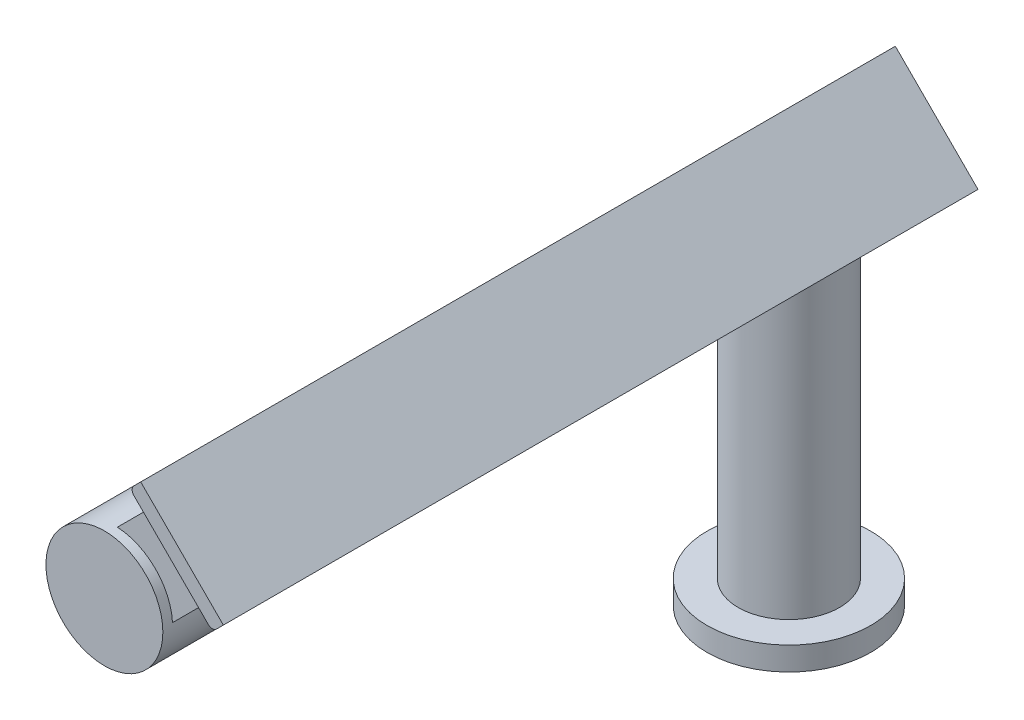
SolidWorks part; units mm, degrees
ref_plane "Front Plane" through (0, 0, 0) normal (0, 0, 1) x (1, 0, 0)
ref_plane "Top Plane" through (0, 0, 0) normal (0, 1, 0) x (1, 0, 0)
ref_plane "Right Plane" through (0, 0, 0) normal (1, 0, 0) x (0, 0, -1)
other "Configuration Table"
sketch "Sketch1" plane through (0, 0, 0) normal (0, 0, 1) x (1, 0, 0)
  line L0 (-231.1886, 129.3652) -> (-234.7241, 125.8297)
  line L1 (-238.9667, 125.8297) -> (-277.1505, 164.0134)
  line L2 (-277.1505, 168.2561) -> (-273.615, 171.7916)
  line L3 (-273.615, 171.7916) -> (-231.1886, 129.3652)
  arc A0 (-234.7241, 125.8297) -> (-238.9667, 125.8297) centre (-236.8454, 127.951) cw
  arc A1 (-277.1505, 164.0134) -> (-277.1505, 168.2561) centre (-275.0292, 166.1347) cw
extrude "Head Flange" add sketch "Sketch1" along normal blind 387.28 from offset 373.18 offset against normal yes
sketch "Sketch2" plane through (0, 0, 0) normal (0, 0, 1) x (1, 0, 0)
  line L0 (-238.2596, 136.4363) -> (-282.1003, 92.5956)
  line L1 (-282.1003, 92.5956) -> (-310.3845, 120.8799)
  line L2 (-310.3845, 120.8799) -> (-266.5439, 164.7205)
  line L3 (-266.5439, 164.7205) -> (-238.2596, 136.4363)
extrude "Primary 2" add sketch "Sketch2" along normal blind 34 from offset 28.9 offset against normal yes
sketch "Sketch3" plane through (0, 0, 0) normal (0, 0, 1) x (1, 0, 0)
  line L0 (-238.2596, 136.4363) -> (-282.1003, 92.5956)
  line L1 (-282.1003, 92.5956) -> (-310.3845, 120.8799)
  line L2 (-310.3845, 120.8799) -> (-266.5439, 164.7205)
  line L3 (-266.5439, 164.7205) -> (-238.2596, 136.4363)
extrude "Primary 4" add sketch "Sketch3" along normal blind 34 from offset 140.66 offset against normal yes
sketch "Sketch4" plane through (0, 0, 0) normal (0, 0, 1) x (1, 0, 0)
  line L0 (-238.2596, 136.4363) -> (-282.1003, 92.5956)
  line L1 (-282.1003, 92.5956) -> (-310.3845, 120.8799)
  line L2 (-310.3845, 120.8799) -> (-266.5439, 164.7205)
  line L3 (-266.5439, 164.7205) -> (-238.2596, 136.4363)
extrude "Primary 6" add sketch "Sketch4" along normal blind 34 from offset 252.42 offset against normal yes
sketch "Sketch5" plane through (0, 0, 0) normal (0, 0, 1) x (1, 0, 0)
  line L0 (-238.2596, 136.4363) -> (-282.1003, 92.5956)
  line L1 (-282.1003, 92.5956) -> (-310.3845, 120.8799)
  line L2 (-310.3845, 120.8799) -> (-266.5439, 164.7205)
  line L3 (-266.5439, 164.7205) -> (-238.2596, 136.4363)
extrude "Primary 8" add sketch "Sketch5" along normal blind 34 from offset 364.18 offset against normal yes
sketch "Sketch6" plane through (0, 0, 0) normal (0, 0, 1) x (1, 0, 0)
  circle A0 centre (-296.2424, 106.7378) radius 30
extrude "Collector" add sketch "Sketch6" along normal blind 377.28 from offset 367.18 offset against normal yes
sketch "Sketch7" plane through (0, 0, 0) normal (0, 1, 0) x (1, 0, 0)
  circle A0 centre (-296.2424, 341.18) radius 26
extrude "Outlet Pipe" add sketch "Sketch7" along normal blind 166.7378 from offset 60 offset against normal yes
sketch "Sketch8" plane through (0, 0, 0) normal (0, 1, 0) x (1, 0, 0)
  circle A0 centre (-296.2424, 341.18) radius 42
extrude "Outlet Flange" add sketch "Sketch8" along normal blind 12 from offset 72 offset against normal yes
sketch "Sketch9" plane through (0, 0, 0) normal (0, 1, 0) x (1, 0, 0)
  circle A0 centre (-296.2424, 341.18) radius 20
extrude "Outlet Bore" cut sketch "Sketch9" along normal blind 169.7378 from offset 73 offset against normal yes
